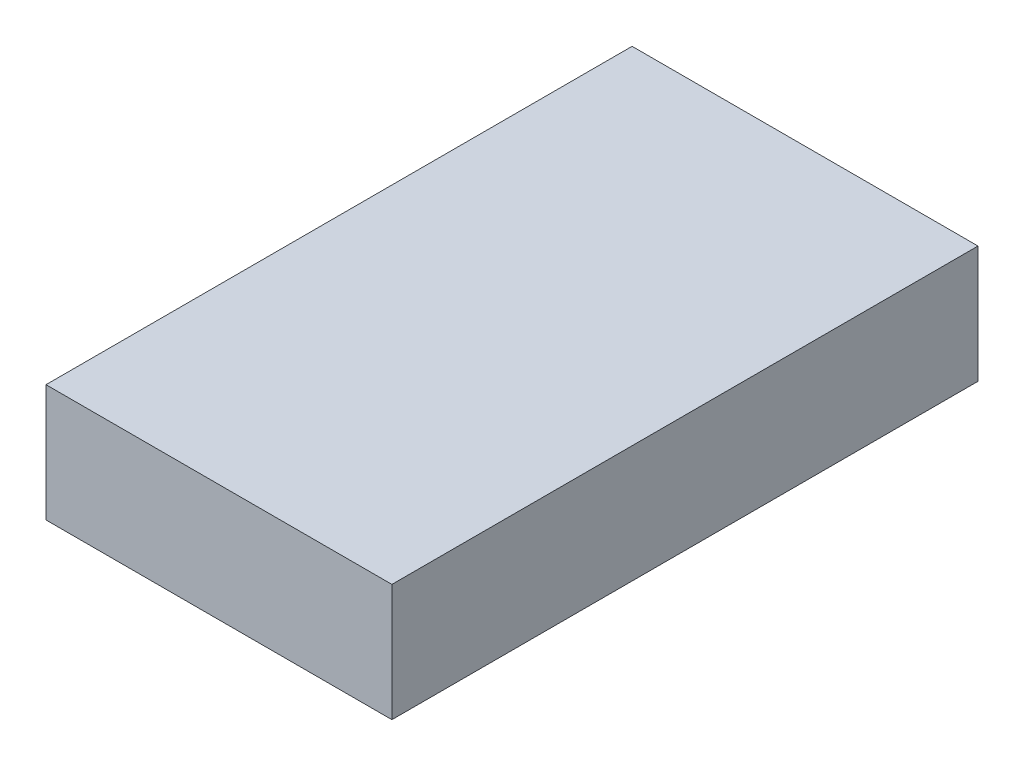
SolidWorks part; units mm, degrees
ref_plane "Front Plane" through (0, 0, 0) normal (0, 0, 1) x (1, 0, 0)
ref_plane "Top Plane" through (0, 0, 0) normal (0, 1, 0) x (1, 0, 0)
ref_plane "Right Plane" through (0, 0, 0) normal (1, 0, 0) x (0, 0, -1)
sketch "Sketch1" plane through (0, 0, 0) normal (0, 1, 0) x (1, 0, 0)
  line L1 (0, 0) -> (29.5209, 0)
  line L2 (0, 0) -> (0, 50.0183)
  line L3 (0, 50.0183) -> (29.5209, 50.0183)
  line L4 (29.5209, 0) -> (29.5209, 50.0183)
extrude "Boss-Extrude1" add sketch "Sketch1" along normal blind 10
